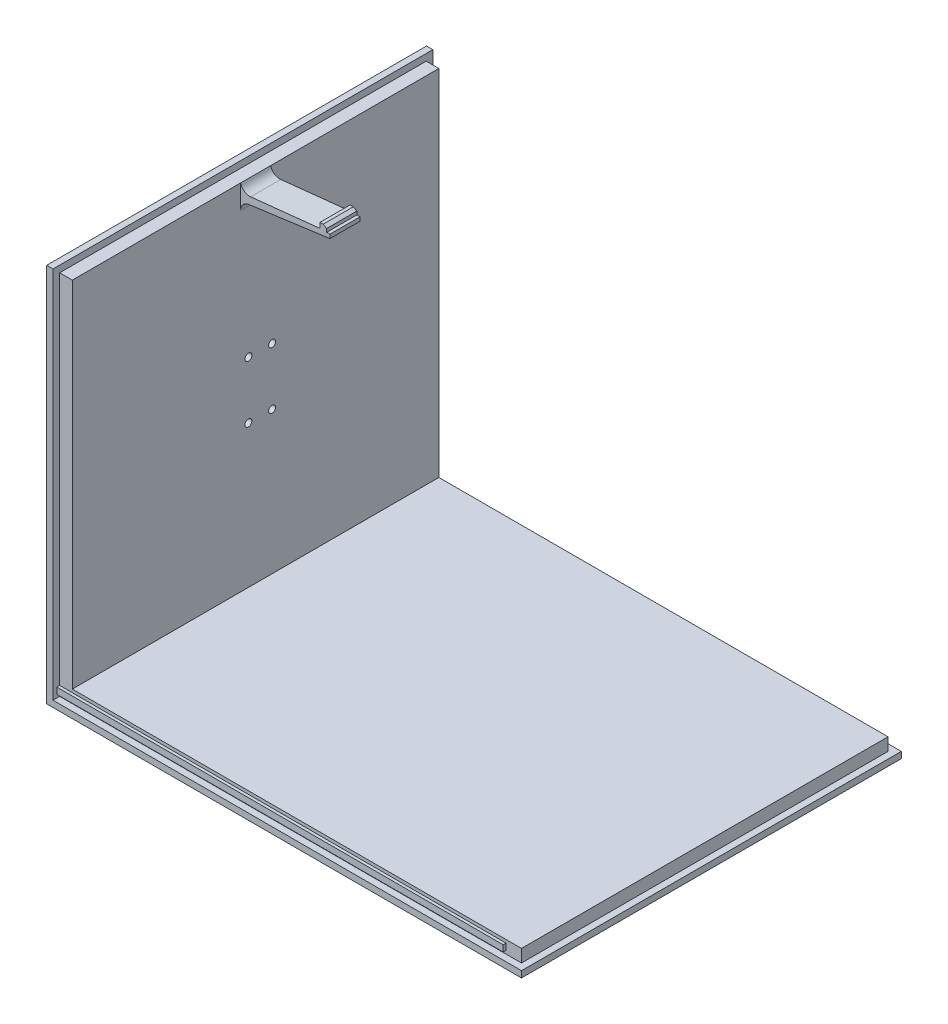
SolidWorks part; units mm, degrees
other "Markup1"
sketch "Sketch5" plane through (-105, 0, 60.5) normal (-0.0451, -0.9984, 0.0353) x (-0.7444, 0.01, -0.6676)
other "Markup2"
sketch "Sketch6" plane through (97, 11, -60) normal (0.0014, 0.7787, -0.6274) x (0.9996, 0.0165, 0.0227)
ref_plane "Front Plane" through (0, 0, 0) normal (0, 0, 1) x (1, 0, 0)
ref_plane "Top Plane" through (0, 0, 0) normal (0, 1, 0) x (1, 0, 0)
ref_plane "Right Plane" through (0, 0, 0) normal (1, 0, 0) x (0, 0, -1)
sketch "Sketch1" plane through (0, 0, 0) normal (0, 1, 0) x (1, 0, 0)
  line L1 (-75, 60) -> (75, 60)
  line L2 (-75, 60) -> (-75, -60)
  line L3 (-75, -60) -> (75, -60)
  line L4 (75, 60) -> (75, -60)
  point P4 (0, 60)
  point P5 (-75, 0)
  dimension "D1" = 120
  dimension "D2" = 150
extrude "Top" add sketch "Sketch1" along normal blind 2
sketch "Sketch2" plane through (0, 2, 0) normal (0, 1, 0) x (1, 0, 0)
  line L0 (-75, 60) -> (-75, -60) construction
  line L1 (-73, -57.9) -> (72.9, -57.9)
  line L2 (-73, -57.9) -> (-73, 57.9)
  line L3 (-73, 57.9) -> (72.9, 57.9)
  line L4 (72.9, -57.9) -> (72.9, 57.9)
  point P7 (72.9, 0)
  dimension "D1" = 115.8
  dimension "D2" = 2
  dimension "D3" = 145.9
extrude "Bottom" add sketch "Sketch2" along normal blind 4
sketch "Sketch8" plane through (0, 2, 0) normal (0, 1, 0) x (1, 0, 0)
  line L0 (-75, -60) -> (75, -60) construction
  line L1 (-75, 60) -> (-73, 60)
  line L2 (-75, 60) -> (-75, -60)
  line L3 (-75, -60) -> (-73, -60)
  line L4 (-73, 60) -> (-73, -60)
  dimension "D1" = 2
extrude "Boss-Extrude2" add sketch "Sketch8" along normal blind 118
sketch "Sketch10" plane through (-73, 0, 0) normal (1, 0, 0) x (0, 0, -1)
  line L1 (-57.9, 6) -> (57.9, 6)
  line L2 (-57.9, 6) -> (-57.9, 117.9)
  line L3 (-57.9, 117.9) -> (57.9, 117.9)
  line L4 (57.9, 6) -> (57.9, 117.9)
  point P4 (0, 117.9)
  dimension "D1" = 111.9
  dimension "D2" = 115.8
  dimension "D3" = 2.1
extrude "Boss-Extrude3" add sketch "Sketch10" along normal blind 4
sketch "Sketch11" plane through (-73, 0, 0) normal (1, 0, 0) x (0, 0, -1)
  line L0 (-57.9, 117.9) -> (-57.9, 2) construction
  line L1 (-57.9, 3) -> (-58.8, 3)
  line L2 (-57.9, 3) -> (-57.9, 5)
  line L3 (-57.9, 5) -> (-58.8, 5)
  line L4 (-58.8, 3) -> (-58.8, 5)
  line L6 (-57.9, 6) -> (-57.9, 2) construction
  line L7 (0, 0) -> (0, 41.6534) construction
  line L8 (58.8, 3) -> (58.8, 5)
  line L9 (57.9, 5) -> (58.8, 5)
  line L10 (57.9, 3) -> (57.9, 5)
  line L11 (57.9, 3) -> (58.8, 3)
  point P10 (-57.9, 4)
  point P11 (-57.9, 4)
  dimension "D1" = 2
  dimension "D2" = 0.9
extrude "Boss-Extrude4" add sketch "Sketch11" along normal blind 141
sketch "Sketch7" plane through (0, 0, 0) normal (0, 0, 1) x (1, 0, 0)
  line L1 (-69, 115.3724) -> (-69, 112.9724)
  line L17 (-69, 112.9724) -> (-40.7801, 116.8)
  line L18 (-41.7801, 119.06) -> (-42.8814, 119.6959)
  line L19 (-42.8814, 119.6959) -> (-43.8814, 119.6959)
  line L20 (-43.8814, 119.6959) -> (-44, 118)
  line L21 (-44, 118) -> (-69, 115.3724)
  line L22 (-41.7801, 118) -> (-41.7801, 119.06)
  line L23 (-41.7801, 118) -> (-40.7801, 118)
  line L24 (-40.7801, 118) -> (-40.7801, 116.8)
  line L25 (-73, 120) -> (-38.2157, 120) construction
  line L26 (-69, 118) -> (-37.8788, 118) construction
  point P55 (-7.5, 67.5)
extrude "Boss-Extrude1" add sketch "Sketch7" along normal mid plane 9.5
fillet "Fillet1" radius 3 2 edges at (-69, 115.3724, 0) (-69, 112.9724, 0)
sketch "Sketch12" plane through (-75, 0, 0) normal (-1, 0, 0) x (0, 0, 1)
  circle A0 centre (-5.225, 51) radius 1.1
  point P2 (0, 0)
  point P3 (0, 0)
  dimension "D1" = 2.2
  dimension "D2" = 51
  dimension "D3" = 5.225
extrude "LED-Mount" cut sketch "Sketch12" against normal blind 6
pattern_linear "LPattern1" count 2 spacing 18 along (0, 1, 0) count 2 spacing 7.5 along (0, 0, 1) of "LED-Mount"
